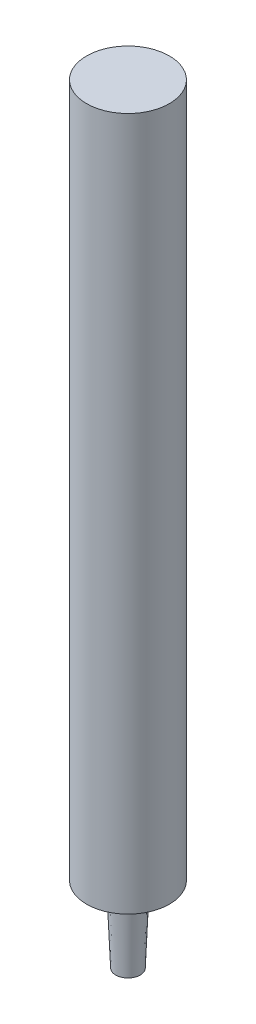
SolidWorks part; units mm, degrees
ref_plane "Front Plane" through (0, 0, 0) normal (0, 0, 1) x (1, 0, 0)
ref_plane "Top Plane" through (0, 0, 0) normal (0, 1, 0) x (1, 0, 0)
ref_plane "Right Plane" through (0, 0, 0) normal (1, 0, 0) x (0, 0, -1)
ref_axis "Axis1" through (-33.0333, 0, 0) along (1, 0, 0)
ref_axis "Axis2" through (0, 24.5224, 0) along (0, -1, 0)
ref_axis "Axis3" through (0, 0, -52.9538) along (0, 0, 1)
sketch "Sketch2" plane through (0, 0, 0) normal (0, 0, 1) x (1, 0, 0)
  line L8 (0, 60.5) -> (0, -60.5)
  line L9 (0, -60.5) -> (2.8, -60.5)
  line L10 (2.8, -60.5) -> (3.35, -46.35)
  line L11 (3.35, -46.35) -> (9.44, -42.5)
  line L14 (9.44, -42.5) -> (9.44, 60.5)
  line L18 (0, 60.5) -> (0, 122)
  line L19 (0, 122) -> (9.44, 122)
  line L20 (9.44, 122) -> (9.44, 60.5)
  dimension "D1" = 121
  dimension "D2" = 2.8
  dimension "D3" = 14.15
  dimension "D4" = 61.5
  dimension "D6" = 9.44
  dimension "D7" = 3.35
  dimension "D8" = 18
revolve "Revolve1" add sketch "Sketch2" angle 360 about L8
scale "Scale1" scale about origin uniform scaling no x scale factor 1.05 y scale factor 1.01 z scale factor 1.05
